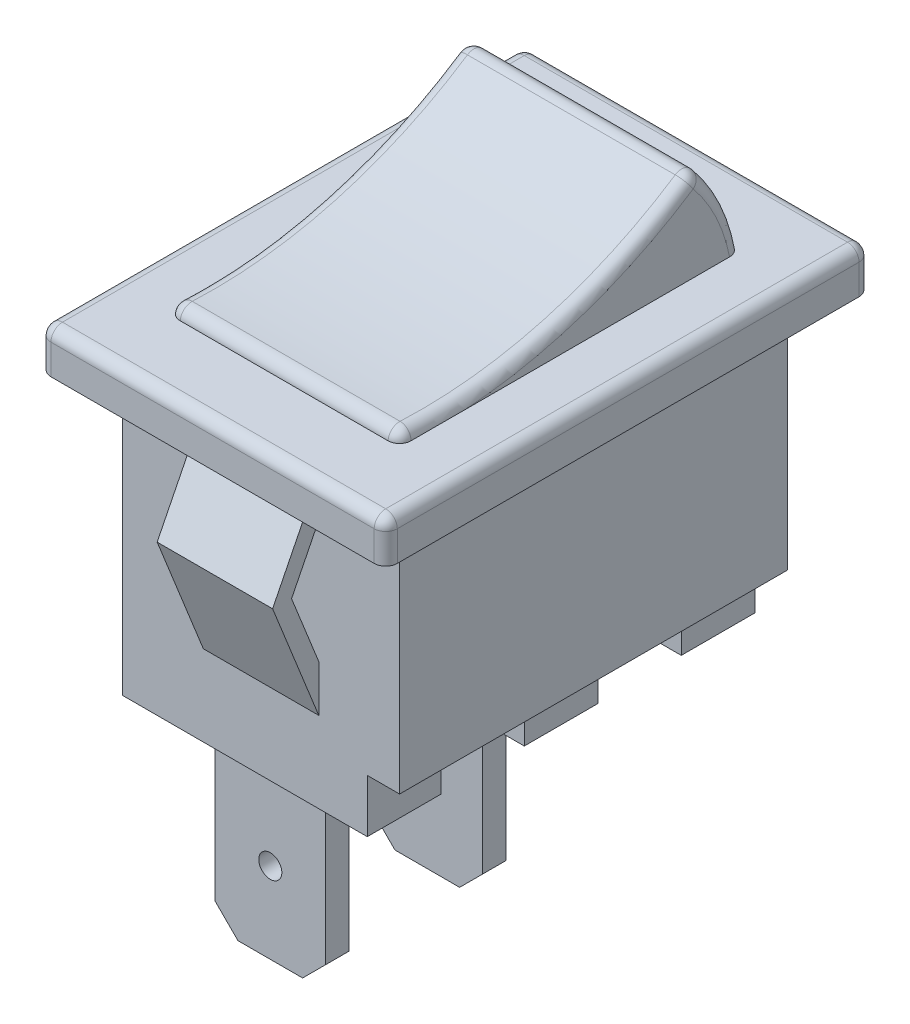
SolidWorks part; units mm, degrees
ref_plane "Front Plane" through (0, 0, 0) normal (0, 0, 1) x (1, 0, 0)
ref_plane "Top Plane" through (0, 0, 0) normal (0, 1, 0) x (1, 0, 0)
ref_plane "Right Plane" through (0, 0, 0) normal (1, 0, 0) x (0, 0, -1)
sketch "Sketch1" plane through (0, 0, 0) normal (0, 1, 0) x (1, 0, 0)
  line L1 (-7.5, -10.5) -> (7.5, -10.5)
  line L2 (-7.5, -10.5) -> (-7.5, 10.5)
  line L3 (-7.5, 10.5) -> (7.5, 10.5)
  line L4 (7.5, -10.5) -> (7.5, 10.5)
  line L5 (-7.5, -10.5) -> (7.5, 10.5) construction
  line L6 (-7.5, 10.5) -> (7.5, -10.5) construction
  point P0 (0, 0)
  dimension "D1" = 15
  dimension "D2" = 21
extrude "Boss-Extrude1" add sketch "Sketch1" along normal blind 1.8
sketch "Sketch2" plane through (0, 0, 0) normal (0, 1, 0) x (1, 0, 0)
  line L1 (-6, 8.4) -> (6, 8.4)
  line L2 (-6, 8.4) -> (-6, -8.4)
  line L3 (-6, -8.4) -> (6, -8.4)
  line L4 (6, 8.4) -> (6, -8.4)
  line L5 (-6, 8.4) -> (6, -8.4) construction
  line L6 (-6, -8.4) -> (6, 8.4) construction
  point P0 (0, 0)
  dimension "D1" = 16.8
  dimension "D2" = 12
extrude "Boss-Extrude2" add sketch "Sketch2" against normal blind 10.2
sketch "Sketch3" plane through (0, -10.2, 0) normal (0, -1, 0) x (1, 0, 0)
  line L0 (-6, -8.4) -> (-6, 8.4) construction
  line L1 (-6, 8.4) -> (4.6, 8.4)
  line L2 (-6, 8.4) -> (-6, 5.2)
  line L3 (-6, 5.2) -> (4.6, 5.2)
  line L4 (4.6, 8.4) -> (4.6, 5.2)
  line L5 (-6, -8.4) -> (4.6, -8.4)
  line L6 (-6, -8.4) -> (-6, -5.2)
  line L7 (-6, -5.2) -> (4.6, -5.2)
  line L8 (4.6, -8.4) -> (4.6, -5.2)
  line L9 (-6, 1.6) -> (4.6, 1.6)
  line L10 (-6, 1.6) -> (-6, -1.6)
  line L11 (-6, -1.6) -> (4.6, -1.6)
  line L12 (4.6, 1.6) -> (4.6, -1.6)
  line L13 (-6, 8.4) -> (4.6, 5.2) construction
  line L14 (-6, 1.6) -> (4.6, -1.6) construction
  line L15 (-6, -5.2) -> (4.6, -8.4) construction
  line L17 (-3.95, 7.3) -> (2.55, 7.3)
  line L18 (-3.95, 7.3) -> (-3.95, 6.3)
  line L19 (-3.95, 6.3) -> (2.55, 6.3)
  line L20 (2.55, 7.3) -> (2.55, 6.3)
  line L21 (-3.95, 7.3) -> (2.55, 6.3) construction
  line L22 (-3.95, 6.3) -> (2.55, 7.3) construction
  line L23 (-3.95, 0.5) -> (2.55, 0.5)
  line L24 (-3.95, 0.5) -> (-3.95, -0.5)
  line L25 (-3.95, -0.5) -> (2.55, -0.5)
  line L26 (2.55, 0.5) -> (2.55, -0.5)
  line L27 (-3.95, 0.5) -> (2.55, -0.5) construction
  line L28 (-3.95, -0.5) -> (2.55, 0.5) construction
  line L29 (-3.95, -7.3) -> (2.55, -7.3)
  line L30 (-3.95, -7.3) -> (-3.95, -6.3)
  line L31 (-3.95, -6.3) -> (2.55, -6.3)
  line L32 (2.55, -7.3) -> (2.55, -6.3)
  line L33 (-3.95, -7.3) -> (2.55, -6.3) construction
  line L34 (-3.95, -6.3) -> (2.55, -7.3) construction
  point P16 (0, 0)
  point P17 (4.6, 0)
  point P19 (-0.7, 6.8)
  point P24 (-0.7, 0)
  point P29 (-0.7, -6.8)
  dimension "D1" = 10.6
  dimension "D2" = 3.2
  dimension "D3" = 6.5
  dimension "D4" = 1
extrude "Boss-Extrude3" add sketch "Sketch3" along normal blind 2.3
sketch "Sketch4" plane through (0, 0, -0.5) normal (0, 0, 1) x (1, 0, 0)
  line L0 (-3.95, -10.2) -> (2.55, -10.2) construction
  line L1 (1.7, -10.2) -> (-3.1, -10.2)
  line L2 (1.7, -10.2) -> (1.7, -19.3)
  line L3 (0.7, -20.3) -> (-2.1, -20.3)
  line L4 (-3.1, -10.2) -> (-3.1, -19.3)
  line L6 (-2.1, -20.3) -> (-3.1, -19.3)
  line L7 (1.7, -19.3) -> (0.7, -20.3)
  line L8 (-6, -12.5) -> (4.6, -12.5) construction
  circle A0 centre (-0.7, -16.8) radius 0.5
  point P1 (-3.1, -20.3)
  point P2 (1.7, -20.3)
  point P4 (-0.7, -10.2)
  point P5 (-0.7, -10.2)
  dimension "D3" = 1
  dimension "D1" = 4.8
  dimension "D2" = 7.8
  dimension "D6" = 3
extrude "Boss-Extrude4" add sketch "Sketch4" along normal blind 1 separate body
ref_plane "Plane1" through (0, 0, 3.4) normal (0, 0, 1) x (1, 0, 0)
mirror "Mirror1" about plane through (0, 0, 3.4) normal (0, 0, 1) of bodies 104
sketch "Sketch5" plane through (0, 0, 0) normal (1, 0, 0) x (0, 0, -1)
  line L0 (-8.4, 0) -> (-10.4, -4)
  line L1 (-10.4, -4) -> (-8.4, -9)
  line L2 (-8.4, -12.5) -> (-8.4, 0) construction
  line L3 (8.4, 0) -> (-8.4, 0) construction
  dimension "D1" = 2
  dimension "D2" = 9
  dimension "D3" = 4
extrude "Extrude-Thin1" add sketch "Sketch5" along normal mid plane 5 thin thin type one direction reverse wall 0.75
mirror "Mirror2" about plane through (0, 0, 0) normal (0, 0, 1) of "Extrude-Thin1"
sketch "Sketch6" plane through (0, 0, 0) normal (1, 0, 0) x (0, 0, -1)
  line L0 (-7.4, 2.3) -> (-7.4, 1.8)
  line L1 (-7.4, 1.8) -> (7.4, 1.8)
  line L2 (10.5, 1.8) -> (-10.5, 1.8) construction
  line L3 (0, 0) -> (0, 1.8) construction
  arc A0 (7.4, 1.8) -> (5.4, 5.8) centre (-0.4702, 0.3649) ccw
  arc A1 (5.4, 5.8) -> (-7.4, 2.3) centre (-5.9764, 22.2493) cw
  dimension "D5" = 20
  dimension "D6" = 8
  dimension "D1" = 14.8
  dimension "D2" = 4
  dimension "D3" = 0.5
  dimension "D4" = 2
extrude "Boss-Extrude5" add sketch "Sketch6" along normal mid plane 10
fillet "Fillet1" radius 0.5 6 edges at (0, 5.8, -5.4) (7.5, 0.9, -10.5) (7.5, 0.9, 10.5) (-7.5, 0.9, 10.5) (-7.5, 0.9, -10.5) (0, 2.3, 7.4)
fillet "Fillet2" radius 0.5 16 edges at (5, 2.969, 0.6594) (5, 5.6332, -5.3884) (-5, 2.969, 0.6594) (-5, 5.6332, -5.3884) (-7.3536, 1.8, -10.3536) (0, 1.8, -10.5) (7.3536, 1.8, -10.3536) (7.5, 1.8, 0) (7.3536, 1.8, 10.3536) (0, 1.8, 10.5) (-7.3536, 1.8, 10.3536) (5, 3.7374, -6.7842) (-5, 3.7374, -6.7842) (-7.5, 1.8, 0) (5, 2.1417, 7.2354) (-5, 2.1417, 7.2354)
